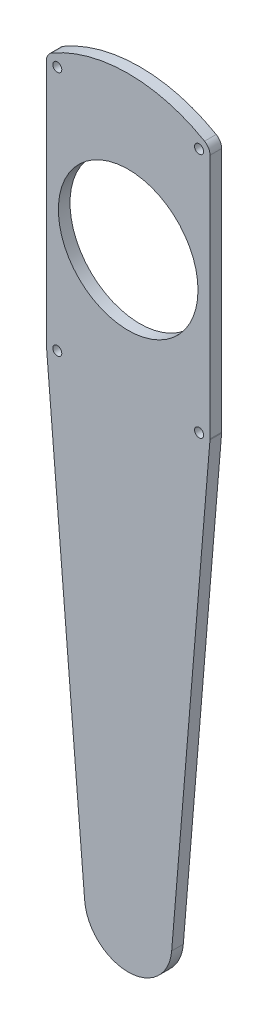
SolidWorks part; units mm, degrees
ref_plane "Front Plane" through (0, 0, 0) normal (0, 0, 1) x (1, 0, 0)
ref_plane "Top Plane" through (0, 0, 0) normal (0, 1, 0) x (1, 0, 0)
ref_plane "Right Plane" through (0, 0, 0) normal (1, 0, 0) x (0, 0, -1)
sketch "Sketch1" plane through (0, 0, 0) normal (0, 0, 1) x (1, 0, 0)
  line L0 (-28.125, 42.2187) -> (-28.125, -42.2187)
  line L1 (28.125, 42.2187) -> (28.125, -42.2187)
  line L2 (0, 0) -> (0, -200) construction
  line L3 (-15.987, -0.6441) -> (-10.7239, -131.2846) construction
  line L4 (-10.7239, -131.2846) -> (-23.5333, -195.2903) construction
  line L5 (10.7239, -131.2846) -> (23.5333, -195.2903) construction
  line L6 (15.987, -0.6441) -> (10.7239, -131.2846) construction
  line L7 (-28.1122, -42.5287) -> (-14.9487, -201.2398)
  line L8 (28.1122, -42.5287) -> (14.9487, -201.2398)
  circle A0 centre (0, 0) radius 24
  arc A1 (-48.7254, 1.5498) -> (-28.125, 39.8189) centre (0, 0) ccw construction
  circle A2 centre (-48.75, 0) radius 1.55 construction
  circle A3 centre (-24.375, 42.2187) radius 1.55
  circle A4 centre (24.375, 42.2187) radius 1.55
  circle A5 centre (48.75, 0) radius 1.55 construction
  circle A6 centre (24.375, -42.2187) radius 1.55
  circle A7 centre (-24.375, -42.2187) radius 1.55
  arc A8 (26.25, 45.4663) -> (-26.25, 45.4663) centre (0, 0) ccw
  arc A9 (-26.25, 45.4663) -> (-28.125, 42.2187) centre (-24.375, 42.2187) ccw
  arc A10 (27.5481, 40.2202) -> (26.25, 45.4663) centre (24.375, 42.2187) ccw
  arc A11 (-27.5481, -40.2202) -> (-26.25, -45.4663) centre (-24.375, -42.2187) ccw
  arc A12 (26.25, -45.4663) -> (27.5481, -40.2202) centre (24.375, -42.2187) ccw
  arc A13 (-21.0577, 43.9674) -> (-26.25, 45.4663) centre (-24.375, 42.2187) ccw construction
  arc A14 (-27.5481, 40.2202) -> (-21.0577, 43.9674) centre (-24.375, 42.2187) ccw construction
  arc A15 (-28.125, 42.2187) -> (-27.5481, 40.2202) centre (-24.375, 42.2187) ccw construction
  arc A16 (-26.25, -45.4663) -> (-21.0577, -43.9674) centre (-24.375, -42.2187) ccw construction
  arc A17 (-21.0577, -43.9674) -> (-27.5481, -40.2202) centre (-24.375, -42.2187) ccw construction
  arc A18 (27.5481, -40.2202) -> (21.0577, -43.9674) centre (24.375, -42.2187) ccw construction
  arc A19 (21.0577, -43.9674) -> (26.25, -45.4663) centre (24.375, -42.2187) ccw construction
  arc A20 (26.25, 45.4663) -> (21.0577, 43.9674) centre (24.375, 42.2187) ccw construction
  arc A21 (21.0577, 43.9674) -> (27.5481, 40.2202) centre (24.375, 42.2187) ccw construction
  arc A22 (26.25, -45.4663) -> (26.25, 45.4663) centre (0, 0) ccw construction
  arc A23 (-26.25, 45.4663) -> (-26.25, -45.4663) centre (0, 0) ccw construction
  arc A24 (-26.25, -45.4663) -> (26.25, -45.4663) centre (0, 0) ccw
  arc A25 (-28.125, 39.8189) -> (-48.7254, 1.5498) centre (0, 0) ccw construction
  circle A26 centre (0, 0) radius 16 construction
  circle A27 centre (0, -200) radius 15
  circle A28 centre (0, -200) radius 24
  point P19 (0, 0)
  point P48 (-15.7634, -201.2266)
  dimension "D1" = 48
  dimension "D2" = 97.5
  dimension "D3" = 3.1
  dimension "D5" = 105
  dimension "D6" = 32
  dimension "D7" = 48
  dimension "D8" = 30
  dimension "D9" = 200
  dimension "D4" = 6
extrude "Boss-Extrude1" add sketch "Sketch1" along normal blind 4 contours A11 A24 A12 L1 A10 A8 A9 L0 A0 A3 A4 A6 A7 region at (-26.591, 43.4981, 0)
extrude "Boss-Extrude2" add sketch "Sketch1<4>" along normal blind 4 contours A28 A12 A24 A11 | A28 A27 | A27 region at (0, -108.8791, 0) region at (0, -183.7653, 0) region at (0, -200, 0)
sketch "Sketch1<4>" plane through (0, 0, 0) normal (0, 0, 1) x (1, 0, 0) same geometry as "Sketch1"
